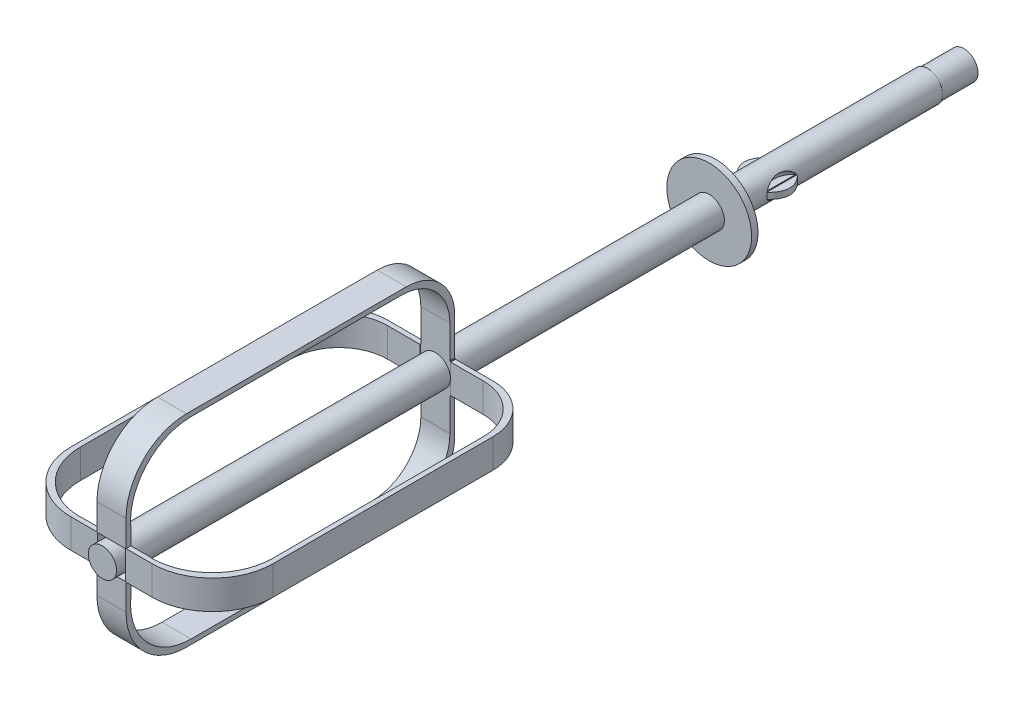
SolidWorks part; units mm, degrees
ref_plane "Front" through (0, 0, 0) normal (0, 0, 1) x (1, 0, 0)
ref_plane "Top" through (0, 0, 0) normal (0, 1, 0) x (1, 0, 0)
ref_plane "Right" through (0, 0, 0) normal (1, 0, 0) x (0, 0, -1)
ref_axis "Center Axis" through (0, 0, -88.99) along (0, 0, 1)
sketch "Sketch1" plane through (0, 0, 0) normal (0, 0, 1) x (1, 0, 0)
  circle A0 centre (0, 0) radius 3.175
  dimension "D1" = 6.35
extrude "Boss-Extrude1" add sketch "Sketch1" along normal blind 177.8
sketch "Sketch2" plane through (0, 0, 0) normal (0, 0, 1) x (1, 0, 0)
  circle A0 centre (0, 0) radius 2.9718
  dimension "D1" = 5.9436
extrude "Boss-Extrude2" add sketch "Sketch2" along normal blind 7.874
sketch "Sketch3" plane through (0, 0, 0) normal (0, 1, 0) x (1, 0, 0)
  line L0 (3.175, -177.8) -> (3.175, 0) construction
  line L1 (-3.175, 0) -> (-3.175, -177.8) construction
  line L2 (-3.175, -38.1) -> (3.175, -38.1)
  line L3 (-3.175, -44.45) -> (3.175, -44.45)
  line L4 (0, -55) -> (0, 55) construction
  parabola Q0 (3.175, -38.1) -> (3.175, -44.45) focus (3.175, -41.275) apex (4.7625, -41.275)
  parabola Q1 (-3.175, -38.1) -> (-3.175, -44.45) focus (-3.175, -41.275) apex (-4.7625, -41.275)
  dimension "D1" = 6.35
extrude "Boss-Extrude3" add sketch "Sketch3" along normal mid plane 1.2954
sketch "Sketch9" plane through (0, 0, 0) normal (1, 0, 0) x (0, 0, -1)
  line L1 (-52.07, 3.175) -> (-53.4162, 3.175)
  line L2 (-52.07, 3.175) -> (-52.07, 8.89)
  line L3 (-52.07, 8.89) -> (-53.4162, 8.89)
  line L4 (-53.4162, 3.175) -> (-53.4162, 8.89)
  line L5 (-52.07, 3.175) -> (-53.4162, 8.89) construction
  line L6 (-52.07, 8.89) -> (-53.4162, 3.175) construction
  line L7 (0, 3.175) -> (-177.8, 3.175) construction
  point P0 (-52.7431, 6.0325)
  dimension "D1" = 1.3462
  dimension "D2" = 5.715
  dimension "D3" = 52.07
extrude "Cut-Extrude2" cut sketch "Sketch2<7>" along normal blind 7.62 from surface flip side to cut contours A0 starting at face at (3.175, 0, 0)
sketch "Sketch2<7>" plane through (0, 0, 0) normal (0, 0, 1) x (1, 0, 0) same geometry as "Sketch2"
revolve "Revolve2" add sketch "Sketch9" angle 360 about axis through (0, 0, -88.99) along (0, 0, 1)
ref_plane "Plane1" through (0, 0, 177.8) normal (0, 0, 1) x (1, 0, 0)
sketch "Sketch31" plane through (0, 0, 177.8) normal (0, 0, 1) x (1, 0, 0)
  circle A0 centre (0, 0) radius 2.9718
extrude "Boss-Extrude6" add sketch "Sketch31" along normal blind 2.921
ref_plane "Plane3" through (0, 0, 109.855) normal (0, 0, 1) x (1, 0, 0)
sketch "Sketch32" plane through (0, 0, 109.855) normal (0, 0, 1) x (1, 0, 0)
  line L1 (-3.1319, 3.2084) -> (3.1319, 3.2084)
  line L2 (-3.1319, 3.2084) -> (-3.1319, -3.2084)
  line L3 (-3.1319, -3.2084) -> (3.1319, -3.2084)
  line L4 (3.1319, 3.2084) -> (3.1319, -3.2084)
  line L5 (-3.1319, 3.2084) -> (3.1319, -3.2084) construction
  line L6 (-3.1319, -3.2084) -> (3.1319, 3.2084) construction
  point P0 (0, 0)
extrude "Boss-Extrude9" add sketch "Sketch32" along normal blind 1.016
sketch "Sketch30" plane through (0, 0, 0) normal (1, 0, 0) x (0, 0, -1)
  line L0 (-177.8, 55) -> (-177.8, -55) construction
  line L24 (-110.871, 3.175) -> (-177.8, 3.175) construction
  line L29 (-120.015, 21.209) -> (-166.116, 21.209)
  line L33 (-110.871, 10.033) -> (-110.871, 3.2084)
  line L37 (-121.031, 20.193) -> (-165.165, 20.193)
  line L39 (-109.855, 11.049) -> (-109.855, 3.2084)
  line L40 (-109.855, 55) -> (-109.855, -55) construction
  line L41 (-110.871, 3.2084) -> (-109.855, 3.2084) construction
  line L44 (-178.816, 8.509) -> (-178.816, 2.9718)
  line L45 (-177.8, 2.9718) -> (-180.721, 2.9718) construction
  line L47 (-177.8, 6.2102) -> (-177.8, 2.2059)
  line L49 (-177.8, 2.2059) -> (-178.816, 2.9718)
  line L50 (-110.871, 3.2084) -> (-109.855, 3.2084)
  arc A0 (-165.165, 20.193) -> (-177.8, 6.2102) centre (-165.165, 7.493) ccw
  arc A1 (-166.116, 21.209) -> (-178.816, 8.509) centre (-166.116, 8.509) ccw
  arc A2 (-110.871, 10.033) -> (-121.031, 20.193) centre (-121.031, 10.033) ccw
  arc A3 (-109.855, 11.049) -> (-120.015, 21.209) centre (-120.015, 11.049) ccw
  point P2 (-177.8, -0.4747)
  point P11 (-166.2178, -5.9728)
  point P20 (-177.8, 18.9102)
  dimension "D4" = 12.7
  dimension "D5" = 12.7
  dimension "D6" = 10.16
  dimension "D7" = 10.16
  dimension "D1" = 1.016
  dimension "D2" = 17.018
extrude "Boss-Extrude10" add sketch "Sketch30" along normal blind 3.048 and the other way blind 3.048
pattern_circular "CirPattern1" count 4 over 360 about axis through (0, 0, -88.99) along (0, 0, 1) of "Boss-Extrude10"
ref_axis "Axis2" through (3.175, 0, 38.1) along (0, 0, 1)
ref_plane "Plane4" through (0, -0.6477, 0) normal (0, -1, 0) x (-1, 0, 0)
sketch "Sketch36" plane through (0, -0.6477, 0) normal (0, -1, 0) x (-1, 0, 0)
  line L2 (-3.2566, -38.1827) -> (-3.2566, -44.3673)
  arc A0 (-3.2566, -38.1827) -> (-3.2566, -44.3673) centre (-0.794, -41.275) ccw
  parabola Q0 (-3.175, -44.45) -> (-3.175, -38.1) focus (-3.175, -41.275) apex (-4.7625, -41.275) construction
  parabola Q1 (-3.175, -44.45) -> (-3.175, -38.1) focus (-3.175, -41.275) apex (-4.7625, -41.275) construction
ref_axis "Axis3" through (3.1082, -0.6477, 38.1) along (0, 0, 1)
revolve "Cut-Revolve3" cut sketch "Sketch36" angle 180 about axis through (3.1082, -0.6477, 38.1) along (0, 0, 1) reverse direction yes
mirror "Mirror1" about plane through (0, 0, 0) normal (0, 1, 0) of "Cut-Revolve3"
mirror "Mirror3" about plane through (0, 0, 0) normal (1, 0, 0) of "Mirror1"
